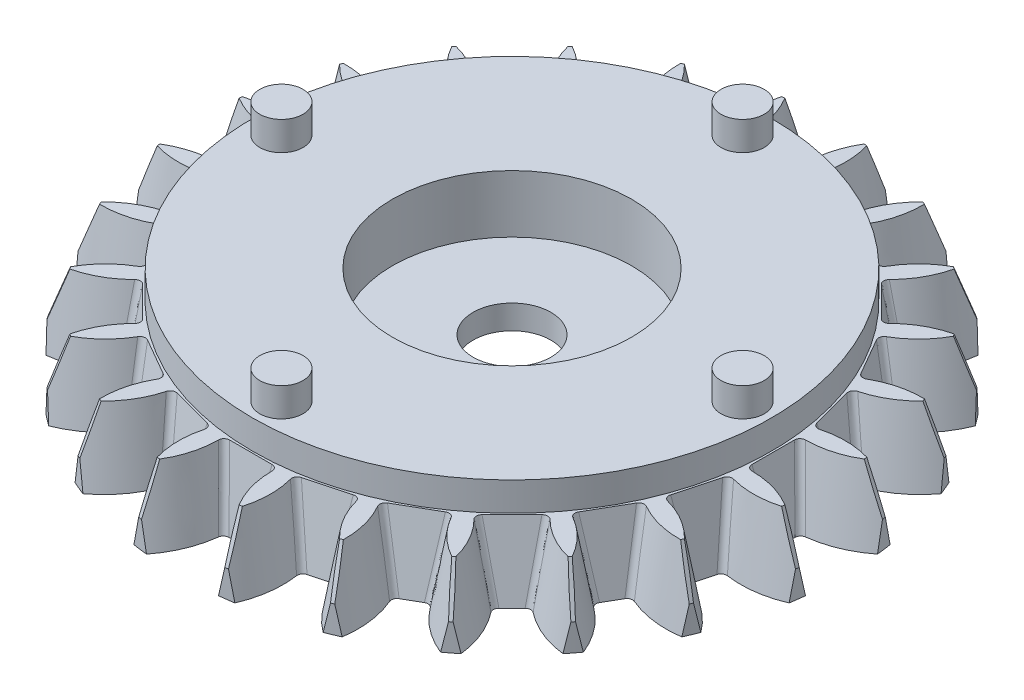
SolidWorks part; units mm, degrees
other "Markup1"
sketch "Sketch6" plane through (11.9816, 3.5, -12) normal (0.4989, 0.8584, -0.1198) x (-0.8086, 0.4112, -0.4208)
other "Markup2"
sketch "Sketch7" plane through (11.9163, 3.5, -11.9163) normal (0.4989, 0.8584, -0.1198) x (-0.8086, 0.4112, -0.4208)
ref_plane "Front Plane" through (0, 0, 0) normal (0, 0, 1) x (1, 0, 0)
ref_plane "Top Plane" through (0, 0, 0) normal (0, 1, 0) x (1, 0, 0)
ref_plane "Right Plane" through (0, 0, 0) normal (1, 0, 0) x (0, 0, -1)
sketch "Sketch1" plane through (0, 0, 0) normal (0, 1, 0) x (1, 0, 0)
  circle A0 centre (0, 0) radius 11.5
  dimension "D1" = 23
extrude "Boss-Extrude1" add sketch "Sketch1" along normal blind 2.5 contours A0
sketch "Sketch2" plane through (0, 2.5, 0) normal (0, 1, 0) x (1, 0, 0)
  circle A0 centre (0, 0) radius 9
  dimension "D1" = 18
extrude "Boss-Extrude2" add sketch "Sketch2" along normal blind 1
sketch "Sketch3" plane through (0, 3.5, 0) normal (0, 1, 0) x (1, 0, 0)
  line L0 (0, 0) -> (0, 8) construction
  line L1 (0, 0) -> (8, 0) construction
  line L2 (0, 0) -> (0, -8) construction
  line L3 (0, 0) -> (-8, 0) construction
  circle A0 centre (0, 8) radius 1.2
  circle A1 centre (8, 0) radius 1.2
  circle A2 centre (0, -8) radius 1.2
  circle A3 centre (-8, 0) radius 1.2
  point P13 (0, 0)
  dimension "D2" = 2.4
  dimension "D1" = 8
  dimension "D3" = 4
extrude "Cut-Extrude1" [suppressed] cut sketch "Sketch3" against normal through all
sketch "Sketch4" plane through (0, 0, 0) normal (0, -1, 0) x (1, 0, 0)
  line L0 (0, 0) -> (0, 11.5) construction
  line L2 (-0.5, 9.5) -> (0.5, 9.5)
  arc A0 (0.5, 9.5) -> (1.25, 11.4319) centre (3.9915, 9.256) cw
  arc A1 (-0.5, 9.5) -> (-1.25, 11.4319) centre (-3.9915, 9.256) ccw
  circle A2 centre (0, 0) radius 11.5 construction
  arc A3 (-1.25, 11.4319) -> (1.25, 11.4319) centre (0, 0) cw
  point P8 (0, 9.5)
  dimension "D3" = 3.5
  dimension "D1" = 2.5
  dimension "D2" = 1
  dimension "D4" = 2
extrude "Cut-Extrude2" cut sketch "Sketch4" against normal up to surface (2.5 mm away) draft 10
fillet "Fillet1" radius 0.2 2 edges
pattern_circular "CirPattern1" count 24 over 360 about axis through (0, 2.5, 0) along (0, -1, 0) of "Cut-Extrude2", "Fillet1"
sketch "Sketch5" plane through (0, 3.5, 0) normal (0, 1, 0) x (1, 0, 0)
  circle A0 centre (0, 0) radius 4.15
  dimension "D1" = 8.3
extrude "Cut-Extrude3" cut sketch "Sketch5" against normal blind 2
sketch "Sketch9" plane through (0, 0, 0) normal (1, 0, 0) x (0, 0, -1)
  line L5 (0, 0) -> (0, 9.7898) construction
  line L6 (10.9311, 2.5) -> (11.75, 2.5)
  line L7 (11.75, 2.5) -> (11.75, 0.25)
  line L8 (11.75, 0.25) -> (10.9311, 2.5)
  line L9 (9, 2.5) -> (-9, 2.5) construction
  dimension "D1" = 23.5
  dimension "D2" = 20
  dimension "D3" = 2.25
revolve "Cut-Revolve1" cut sketch "Sketch9" angle 360 about L5
sketch "Sketch10" [suppressed] plane through (0, 0, 0) normal (0, -1, 0) x (1, 0, 0)
  circle A0 centre (0, 8) radius 1.9
  circle A1 centre (-8, 0) radius 1.9
  circle A2 centre (8, 0) radius 1.9
  circle A3 centre (0, -8) radius 1.9
  dimension "D1" = 3.8
extrude "Cut-Extrude5" [suppressed] cut sketch "Sketch10" against normal blind 2
sketch "Sketch11" [suppressed] plane through (0, 0, 0) normal (0, 0, 1) x (1, 0, 0)
  line L0 (-9.2, 0) -> (-6.8, 0) construction
  line L1 (-9.2, 0) -> (-6.8, 0) construction
  line L2 (-8, 0) -> (-8, 10)
  line L3 (-8, 10) -> (-9, 10)
  line L4 (-9, 10) -> (-9, 1)
  line L5 (-9, 1) -> (-10, 0)
  line L6 (-10, 0) -> (-8, 0)
  dimension "D1" = 45
  dimension "D2" = 1
  dimension "D3" = 2
  dimension "D4" = 10
revolve "Cut-Revolve2" [suppressed] cut sketch "Sketch11" angle 360 about L2
pattern_circular "CirPattern2" [suppressed] count 4 over 360
sketch "Sketch12" plane through (0, 0, 0) normal (0, 0, 1) x (1, 0, 0)
  line L0 (0, 0) -> (0, 3.5)
  line L1 (0, 3.5) -> (1.35, 3.5)
  line L2 (1.35, 3.5) -> (1.35, 0.664)
  line L3 (1.35, 0.664) -> (2.5, 0)
  line L4 (2.5, 0) -> (0, 0)
  line L5 (0, 0) -> (0, 8.7784) construction
  line L6 (4.15, 3.5) -> (-4.15, 3.5) construction
  dimension "D1" = 5
  dimension "D2" = 60
  dimension "D3" = 2.7
revolve "Cut-Revolve3" cut sketch "Sketch12" angle 360 about L5
sketch "Sketch13" plane through (0, 3.5, 0) normal (0, 1, 0) x (1, 0, 0)
  circle A0 centre (0, 0) radius 8 construction
  circle A1 centre (0, 8) radius 0.75
  circle A2 centre (8, 0) radius 0.75
  circle A3 centre (0, -8) radius 0.75
  circle A4 centre (-8, 0) radius 0.75
  dimension "D1" = 16
  dimension "D2" = 1.5
extrude "Boss-Extrude3" add sketch "Sketch13" along normal blind 1
